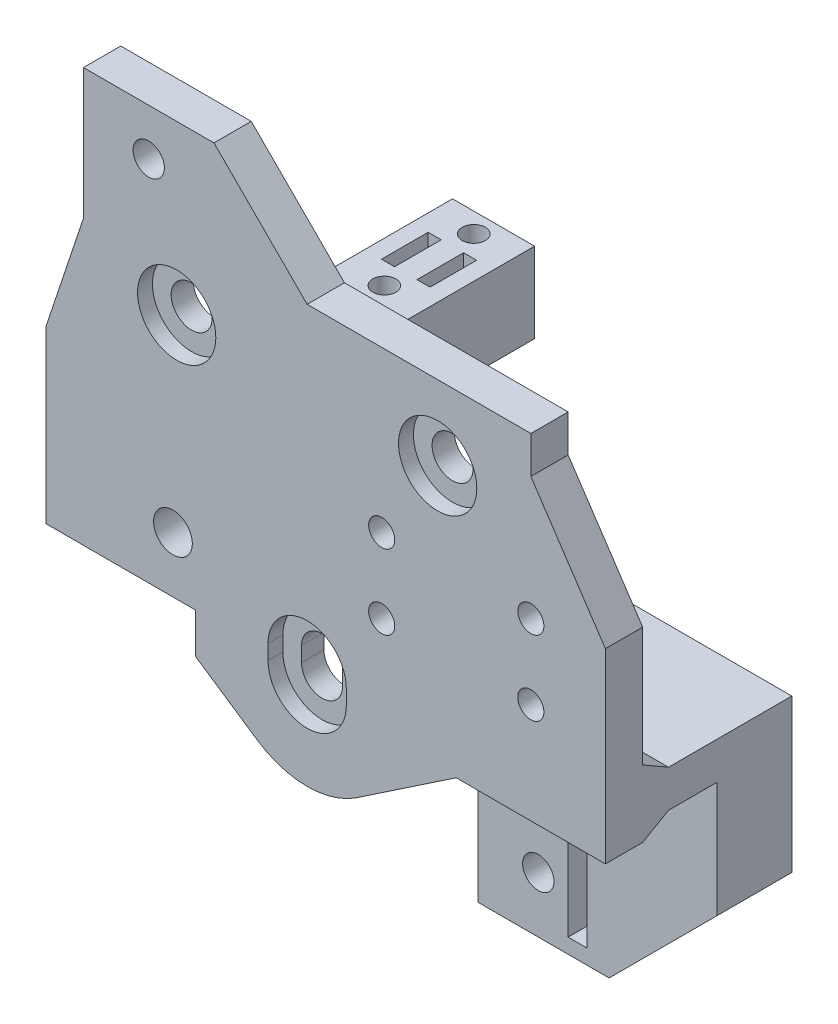
SolidWorks part; units mm, degrees
ref_plane "Спереди" through (0, 0, 0) normal (0, 0, 1) x (1, 0, 0)
ref_plane "Сверху" through (0, 0, 0) normal (0, 1, 0) x (1, 0, 0)
ref_plane "Справа" through (0, 0, 0) normal (1, 0, 0) x (0, 0, -1)
sketch "Эскиз1" plane through (0, 0, 0) normal (0, 0, 1) x (1, 0, 0)
  line L0 (-12.5, 35) -> (0, 22.5)
  line L5 (-30, -22.5) -> (30, -22.5)
  line L6 (-30, -22.5) -> (-30, 22.5)
  line L7 (-30, 22.5) -> (30, 22.5)
  line L8 (30, -22.5) -> (30, 22.5)
  line L9 (-30, -22.5) -> (30, 22.5) construction
  line L10 (-30, 22.5) -> (30, -22.5) construction
  line L12 (-17.5, 12.5) -> (17.5, 12.5) construction
  line L13 (-20, -22.5) -> (-6.7023, -31.4538)
  line L14 (0, -55) -> (0, 55) construction
  line L15 (20, -22.5) -> (6.7023, -31.4538)
  line L16 (-17.5, 12.5) -> (-17.5, -21.5) construction
  line L20 (-35, 2.5) -> (-30, 17.5)
  line L21 (-30, -22.5) -> (-35, -22.5)
  line L22 (-30, -22.5) -> (-30, 2.5)
  line L23 (-30, 2.5) -> (-35, 2.5)
  line L24 (-35, -22.5) -> (-35, 2.5)
  line L25 (-35, -20.5) -> (-15, -20.5)
  line L26 (-15, -20.5) -> (-15, -25.8667)
  line L27 (40, -22.5) -> (40, 2.5)
  line L28 (30, 2.5) -> (40, 2.5)
  line L29 (30, -22.5) -> (30, 2.5)
  line L30 (30, -22.5) -> (40, -22.5)
  line L31 (40, 2.5) -> (30, 17.5)
  line L32 (-30, 22.5) -> (-12.5, 22.5)
  line L33 (-30, 22.5) -> (-30, 35)
  line L34 (-30, 35) -> (-12.5, 35)
  line L35 (-12.5, 22.5) -> (-12.5, 35)
  line L36 (-2.75, -19.5) -> (-2.75, -21.5)
  line L37 (2.75, -19.5) -> (2.75, -21.5)
  circle A0 centre (0, -21.5) radius 12
  circle A1 centre (-17.5, 12.5) radius 2.75
  circle A2 centre (17.5, 12.5) radius 2.75
  circle A3 centre (0, -21.5) radius 2.75
  circle A4 centre (0, 14.5) radius 2.1 construction
  circle A5 centre (0, 4.5) radius 2.1 construction
  circle A6 centre (-21.25, 28.75) radius 2.1
  circle A7 centre (0, -19.5) radius 2.75
  point P0 (0, 0)
  point P5 (0, 12.5)
  point P9 (0, -33.5)
  point P26 (-17.5, -4.5)
  point P46 (-30, 28.75)
  point P48 (-21.25, 35)
  dimension "D4" = 24
  dimension "D6" = 15
  dimension "D8" = 5.5
  dimension "D12" = 4.2
  dimension "D21" = 4.2
  dimension "D1" = 60
  dimension "D2" = 45
  dimension "D3" = 10
  dimension "D5" = 35
  dimension "D7" = 34
  dimension "D9" = 20
  dimension "D10" = 12.5
  dimension "D11" = 10
  dimension "D13" = 8
  dimension "D14" = 10
  dimension "D15" = 25
  dimension "D16" = 5
  dimension "D17" = 43
  dimension "D18" = 20
  dimension "D19" = 17.5
  dimension "D20" = 45
  dimension "D22" = 2
extrude "Бобышка-Вытянуть1" add sketch "Эскиз1" along normal blind 5
sketch "Эскиз2" plane through (0, 0, 0) normal (0, 0, -1) x (-1, 0, 0)
  line L1 (-40, -15.5) -> (35, -15.5)
  line L2 (-40, -15.5) -> (-40, -20.5)
  line L3 (-40, -20.5) -> (35, -20.5)
  line L4 (35, -15.5) -> (35, -20.5)
  line L6 (0, 22.5) -> (-30, 22.5) construction
  line L7 (35, -20.5) -> (35, 2.5) construction
  line L8 (-7.6151, -20.5) -> (7.6151, -20.5)
  line L9 (-7.6151, -20.5) -> (-7.6151, -15.5)
  line L10 (-7.6151, -15.5) -> (7.6151, -15.5)
  line L11 (7.6151, -20.5) -> (7.6151, -15.5)
  line L12 (-7.6151, -20.5) -> (7.6151, -15.5) construction
  line L13 (-7.6151, -15.5) -> (7.6151, -20.5) construction
  line L14 (-10.3923, -20.5) -> (-10.3923, -15.5)
  line L15 (0, -12.5824) -> (0, -25.0007) construction
  line L16 (10.3923, -20.5) -> (10.3923, -15.5)
  line L17 (-5.5, 19.5) -> (5.5, 19.5)
  line L18 (-5.5, 19.5) -> (-5.5, 8.75)
  line L19 (-5.5, 8.75) -> (5.5, 8.75)
  line L20 (5.5, 19.5) -> (5.5, 8.75)
  line L21 (-17.5, 12.5) -> (-17.5, -18) construction
  line L22 (-42.6784, -12.75) -> (42.6784, -12.75)
  line L23 (-42.6784, -12.75) -> (-42.6784, 7.25)
  line L24 (-42.6784, 7.25) -> (42.6784, 7.25)
  line L25 (42.6784, -12.75) -> (42.6784, 7.25)
  line L26 (-42.6784, -12.75) -> (42.6784, 7.25) construction
  line L27 (-42.6784, 7.25) -> (42.6784, -12.75) construction
  line L28 (0, 22.5) -> (-30, 22.5) construction
  line L29 (-40, -22.5) -> (-40, 2.5) construction
  circle A0 centre (0, -21.5) radius 8 construction
  circle A1 centre (0, -21.5) radius 12
  circle A2 centre (-17.5, 12.5) radius 8 construction
  circle A3 centre (17.5, 12.5) radius 8 construction
  circle A4 centre (-17.5, 12.5) radius 12
  circle A5 centre (17.5, 12.5) radius 12
  point P10 (0, -18)
  point P43 (0, -2.75)
  point P49 (-17.5, -2.75)
  point P50 (-42.6784, -2.75)
  line M34 (35, -20.5) -> (35, 2.5)
  line M40 (15, -20.5) -> (35, -20.5)
  line M62 (-40, 2.5) -> (-40, -22.5)
  dimension "D3" = 16
  dimension "D1" = 5
  dimension "D2" = 38
  dimension "D5" = 4
  dimension "D6" = 20
  dimension "D7" = 1.5
  dimension "D8" = 3
  dimension "D4" = 4
extrude "Бобышка-Вытянуть2" add sketch "Эскиз2" along normal blind 20 contours L20 L17 L18 L19 | A1 L3 L1 M40 M34 | L3 A1 L16 | L14 A1 L3 | A1 L1 L3 M62
ref_plane "Плоскость4" through (0, -4.5, 0) normal (0, 1, 0) x (1, 0, 0)
chamfer "Фаска1" distance 2 angle 60 6 edges at (25.1962, -20.5, 0) (10.3923, -18, 0) (25.1962, -15.5, 0) (-12.6962, -20.5, 0) (-10.3923, -18, 0) (-22.6962, -15.5, 0)
sketch "Эскиз8" plane through (0, 0, 5) normal (0, 0, 1) x (1, 0, 0)
  line L0 (-5.25, -19.5) -> (-5.25, -21.5)
  line L1 (5.25, -19.5) -> (5.25, -21.5)
  circle A0 centre (0, -19.5) radius 5.25
  circle A8 centre (-17.5, 12.5) radius 5.25
  circle A10 centre (17.5, 12.5) radius 5.25
  circle A11 centre (17.5, 12.5) radius 5.25
  circle A14 centre (0, -21.5) radius 5.25
  arc M4 (2.75, -21.5) -> (-2.75, -21.5) centre (0, -21.5) cw
  circle M18 centre (-17.5, 12.5) radius 2.75
  circle M19 centre (17.5, 12.5) radius 2.75
  line M30 (2.75, -19.5) -> (2.75, -21.5)
  line M31 (-2.75, -21.5) -> (-2.75, -19.5)
  arc M32 (-2.75, -19.5) -> (2.75, -19.5) centre (0, -19.5) cw
  dimension "D2" = 2.5
extrude "Вырез-Вытянуть3" cut sketch "Эскиз8" against normal blind 2 contours A14 A0 M31 M32 M30 | A14 A0 M31 | A14 A0 M30 M4 M31 | A0 A14 M30 | A14 A0 L0 | A14 L1 A0 | A11 M19 | A8 M18
sketch "Эскиз9" plane through (0, 22.5, 0) normal (0, 1, 0) x (1, 0, 0)
  line L0 (9.875, 14.3) -> (9.875, 8.4) construction
  line L1 (-1.5, 8.225) -> (1.5, 8.225)
  line L2 (-1.5, 8.225) -> (-1.5, 14.475)
  line L3 (-1.5, 14.475) -> (1.5, 14.475)
  line L4 (1.5, 8.225) -> (1.5, 14.475)
  line L5 (-1.5, 8.225) -> (1.5, 14.475) construction
  line L6 (-1.5, 14.475) -> (1.5, 8.225) construction
  line L7 (9.875, 14.3) -> (9.875, 8.4)
  line L9 (-3.25, 8.225) -> (3.25, 8.225)
  line L10 (-3.25, 8.225) -> (-3.25, 14.475)
  line L11 (-3.25, 14.475) -> (3.25, 14.475)
  line L12 (3.25, 8.225) -> (3.25, 14.475)
  line L13 (-3.25, 8.225) -> (3.25, 14.475) construction
  line L14 (-3.25, 14.475) -> (3.25, 8.225) construction
  point P0 (0, 11.35)
  point P5 (0, 11.35)
  point P9 (9.875, 11.35)
  point P10 (1.5, 11.35)
  dimension "D1" = 3
  dimension "D2" = 6.25
  dimension "D3" = 1.75
extrude "Вырез-Вытянуть4" cut sketch "Эскиз9" against normal up to next contours L11 L10 L9 L2 | L9 L12 L11 L4
sketch "Эскиз10" plane through (0, 22.5, 0) normal (0, 1, 0) x (1, 0, 0)
  line L0 (0, 17.35) -> (0, 5.35) construction
  line L2 (-1.5, 14.475) -> (1.5, 14.475) construction
  line L3 (5.5, 20) -> (-5.5, 20) construction
  line L4 (3.25, 14.475) -> (1.5, 14.475) construction
  circle A0 centre (0, 17.35) radius 1.55
  circle A1 centre (0, 5.35) radius 1.55
  point P7 (0, 11.35)
  point P10 (0, 14.475)
  dimension "D1" = 3.1
  dimension "D2" = 12
  dimension "D3" = 2.65
extrude "Вырез-Вытянуть5" cut sketch "Эскиз10" against normal blind 8
fillet "Скругление1" radius 1 4 edges at (1.5, 8.75, -11.35) (-1.5, 8.75, -11.35) (3.25, 8.75, -11.35) (-3.25, 8.75, -11.35)
chamfer "Фаска2" distance 3 angle 45 3 edges at (-5.5, 14.125, 0) (5.5, 14.125, 0) (0, 19.5, 0)
sketch "Эскиз11" plane through (0, -20.5, 0) normal (0, -1, 0) x (1, 0, 0)
  line L0 (-27.5, 0) -> (-27.5, -15) construction
  line L2 (-35, 5) -> (-15, 5) construction
  line L3 (-35, 5) -> (-35, -20) construction
  circle A0 centre (-27.5, -15) radius 1.6
  circle A1 centre (-27.5, 0) radius 1.6
  dimension "D2" = 3.2
  dimension "D1" = 15
  dimension "D3" = 5
  dimension "D4" = 7.5
extrude "Вырез-Вытянуть6" cut sketch "Эскиз11" against normal blind 6
sketch "Эскиз12" plane through (0, 0, -20) normal (0, 0, -1) x (-1, 0, 0)
  line L0 (10.3923, -20.5) -> (35, -20.5) construction
  line L1 (23.75, -20.5) -> (31.25, -20.5)
  line L2 (23.75, -20.5) -> (23.75, -25.545)
  line L3 (23.75, -25.545) -> (31.25, -25.545)
  line L4 (31.25, -20.5) -> (31.25, -25.545)
  line L5 (24, -22.8254) -> (24, -20.9) construction
  line L6 (31, -22) -> (31, -22.8204) construction
  line L7 (30.7, -25.295) -> (24.3, -25.295) construction
  line L8 (21.75, -20.5) -> (21.75, -27.545)
  line L9 (21.75, -27.545) -> (33.25, -27.545)
  line L10 (33.25, -20.5) -> (33.25, -27.545)
  line L11 (21.75, -20.5) -> (23.75, -20.5)
  line L12 (31.25, -20.5) -> (33.25, -20.5)
  line M6 (10.3923, -20.5) -> (35, -20.5)
  dimension "D1" = 0.25
  dimension "D2" = 0.25
  dimension "D3" = 0.25
  dimension "D4" = 2
extrude "Бобышка-Вытянуть3" add sketch "Эскиз12" against normal blind 3 contours L10 L4 L3 L2 L8 L9 M6
chamfer "Фаска3" distance 2 angle 45 2 edges at (-21.75, -20.5, -18.5) (-33.25, -20.5, -18.5)
chamfer "Фаска4" distance 0.5 angle 45 2 edges at (-31.25, -20.5, -18.5) (-23.75, -20.5, -18.5)
chamfer "Фаска5" distance 0.5 angle 45 2 edges at (-23.75, -25.545, -18.5) (-31.25, -25.545, -18.5)
sketch "Эскиз14" plane through (0, 0, -20) normal (0, 0, -1) x (-1, 0, 0)
  line L0 (-25.5, -35.5) -> (-25.5, -50.5)
  line L1 (-40, -35.5) -> (-20, -35.5)
  line L2 (-40, -35.5) -> (-40, -50.5)
  line L3 (-40, -50.5) -> (-20, -50.5)
  line L4 (-20, -35.5) -> (-20, -50.5)
  line L5 (-40, -20.5) -> (-20, -20.5)
  line L6 (-40, -20.5) -> (-40, -35.5)
  line L7 (-40, -35.5) -> (-20, -35.5)
  line L8 (-20, -20.5) -> (-20, -35.5)
  line L9 (-20, -35.5) -> (-7.8923, -35.5)
  line L10 (-20, -35.5) -> (-20, -50.5)
  line L11 (-20, -50.5) -> (-7.8923, -50.5)
  line L12 (-7.8923, -35.5) -> (-7.8923, -50.5)
  line L13 (-10.3923, -20.5) -> (-20, -20.5)
  line L14 (-10.3923, -20.5) -> (-10.3923, -35.5)
  line L15 (-10.3923, -35.5) -> (-20, -35.5)
  line L16 (-20, -20.5) -> (-20, -35.5)
  line L17 (-22.5, -48.5) -> (-20, -48.5)
  line L18 (-22.5, -48.5) -> (-22.5, -37.5)
  line L19 (-22.5, -37.5) -> (-20, -37.5)
  line L20 (-20, -48.5) -> (-20, -37.5)
  line L21 (-22.5, -48.5) -> (-20, -37.5) construction
  line L22 (-22.5, -37.5) -> (-20, -48.5) construction
  circle A0 centre (-16, -43) radius 2.1
  point P12 (-21.25, -43)
  line M7 (-40, -20.5) -> (-10.3923, -20.5)
  dimension "D4" = 4.2
  dimension "D1" = 15
  dimension "D2" = 20
  dimension "D3" = 24
  dimension "D5" = 7.5
  dimension "D6" = 15
  dimension "D7" = 2.5
  dimension "D8" = 11
  dimension "D9" = 2.5
  dimension "D10" = 3
extrude "Бобышка-Вытянуть4" add sketch "Эскиз14" along normal blind 3 from offset 10 contours L8 L6 L1 M7 | L12 L9 L4 L11 A0 | L14 L8 L9 M7 | L18 L19 L4 L1 L2 L3 L10 L17 offset against normal yes
sketch "Эскиз15" plane through (0, 0, -10) normal (0, 0, 1) x (1, 0, 0)
  line L1 (16, -38) -> (23, -38)
  line L2 (16, -38) -> (16, -43)
  line L3 (16, -43) -> (23, -43)
  line L4 (23, -38) -> (23, -43)
  line L5 (40, -20.5) -> (10.3923, -20.5) construction
  line L6 (20, -48.5) -> (20, -37.5) construction
  dimension "D1" = 4
  dimension "D2" = 7
  dimension "D3" = 17.5
  dimension "D4" = 5
extrude "Вырез-Вытянуть7" [suppressed] cut sketch "Эскиз15" against normal blind 1.5
chamfer "Фаска6" distance 15 angle 45 2 edges at (25.1962, -20.5, -13) (25.1962, -20.5, -20)
sketch "Эскиз16" plane through (0, 0, 5) normal (0, 0, 1) x (1, 0, 0)
  line L0 (-15, -20.5) -> (-15, -25.8667) construction
  line L1 (-35, -20.5) -> (-15, -20.5) construction
  circle A0 centre (-18, -13) radius 2.6
  dimension "D1" = 5.2
  dimension "D25" = 3
  dimension "2ё" = 7.5
extrude "Вырез-Вытянуть8" cut sketch "Эскиз16" against normal up to vertex (8.4641 mm away) up to point (-10.3923, -15.5, -3.4641)
sketch "Эскиз17" plane through (0, 0, 0) normal (0, 0, -1) x (-1, 0, 0)
  line L1 (-30, 1) -> (-10, 1) construction
  line L2 (-30, 1) -> (-30, -9) construction
  line L3 (-30, -9) -> (-10, -9) construction
  line L4 (-10, 1) -> (-10, -9) construction
  circle A0 centre (-30, 1) radius 1.75
  circle A1 centre (-10, 1) radius 1.75
  circle A2 centre (-10, -9) radius 1.75
  circle A3 centre (-30, -9) radius 1.75
  dimension "D1" = 3.5
  dimension "D2" = 20
  dimension "D3" = 10
  dimension "D4" = 1
  dimension "D5" = 10
extrude "Вырез-Вытянуть9" cut sketch "Эскиз17" against normal through all
chamfer "Фаска7" distance 2 angle 45 4 edges at (28.25, -9, 0) (28.25, 1, 0) (8.25, -9, 0) (8.25, 1, 0)
sketch "Эскиз18" plane through (40, 0, 0) normal (1, 0, 0) x (0, 0, -1)
  line L1 (13, -35.5) -> (20, -35.5)
  line L2 (13, -35.5) -> (13, -20.5)
  line L3 (13, -20.5) -> (20, -20.5)
  line L4 (20, -35.5) -> (20, -20.5)
extrude "Бобышка-Вытянуть5" add sketch "Эскиз18" against normal blind 2
chamfer "Фаска8" [suppressed] distance 4 angle 45
chamfer "Фаска9" distance 2.5 angle 45 1 edges at (10.3923, -35.5, -11.5)
chamfer "Фаска10" distance 15 angle 45 1 edges at (25.5, -35.5, -11.5)
